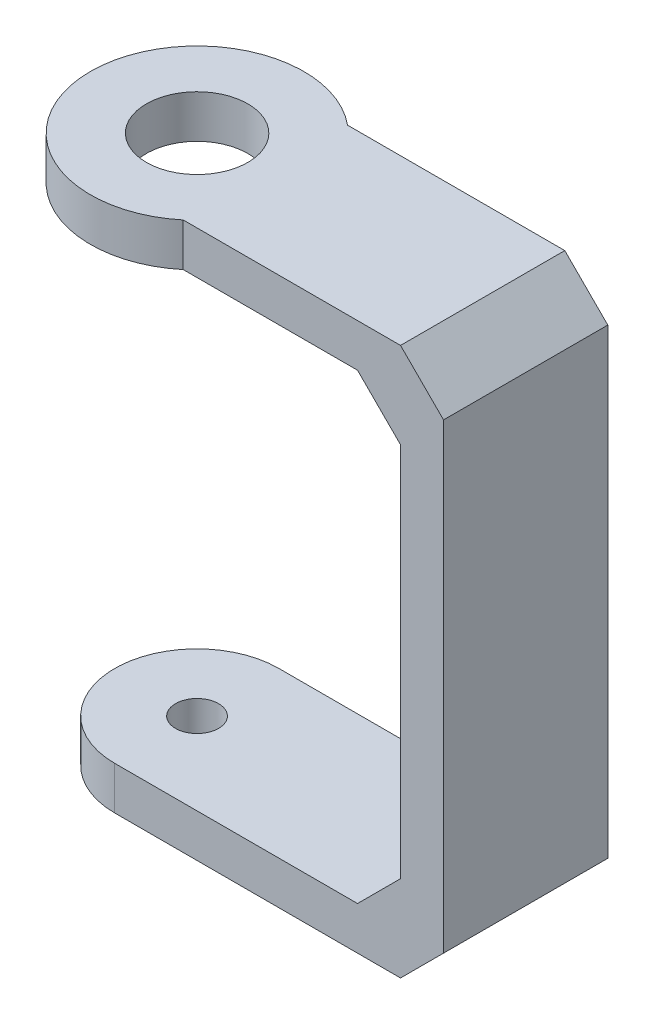
SolidWorks part; units mm, degrees
ref_plane "Front Plane" through (0, 0, 0) normal (0, 0, 1) x (1, 0, 0)
ref_plane "Top Plane" through (0, 0, 0) normal (0, 1, 0) x (1, 0, 0)
ref_plane "Right Plane" through (0, 0, 0) normal (1, 0, 0) x (0, 0, -1)
sketch "Sketch1" plane through (0, 0, 0) normal (0, 0, 1) x (1, 0, 0)
  line L0 (23.7361, 38.9968) -> (26.7361, 35.9968)
  line L1 (26.7361, 35.9968) -> (26.7361, 3.7768)
  line L2 (26.7361, 3.7768) -> (23.7361, 0.7768)
  line L3 (23.7361, 0.7768) -> (20.7361, 3.7768)
  line L4 (20.7361, 3.7768) -> (23.7361, 6.7768)
  line L7 (23.7361, 6.7768) -> (23.7361, 32.9968)
  line L8 (23.7361, 32.9968) -> (20.7361, 35.9968)
  line L9 (20.7361, 35.9968) -> (23.7361, 38.9968)
  point P2 (0, 0)
extrude "Boss-Extrude1" add sketch "Sketch1" along normal blind 5.73 and the other way blind 5.73
sketch "Sketch6" plane through (0, 0, 5.73) normal (0, 0, 1) x (1, 0, 0)
  line L0 (20.7361, 3.7768) -> (8.5761, 3.7768)
  line L1 (23.7361, 0.7768) -> (20.7361, 0.7768)
  line L3 (8.5761, 3.7768) -> (8.5761, 0.7768)
  line L4 (8.5761, 0.7768) -> (20.7361, 0.7768)
  line L5 (23.7361, 0.7768) -> (20.7361, 3.7768)
extrude "Boss-Extrude5" add sketch "Sketch6" against normal blind 11.46 contours L1 L4 L3 L0 L5
sketch "Sketch8" plane through (0, 0, 5.73) normal (0, 0, 1) x (1, 0, 0)
  line L1 (20.7361, 38.9968) -> (23.7361, 38.9968)
  line L2 (20.7361, 38.9968) -> (8.5761, 38.9968)
  line L3 (8.5761, 38.9968) -> (8.5761, 35.9968)
  line L4 (8.5761, 35.9968) -> (20.7361, 35.9968)
  line L5 (23.7361, 38.9968) -> (20.7361, 35.9968)
extrude "Boss-Extrude8" add sketch "Sketch8" against normal blind 11.46
sketch "Sketch9" plane through (0, 38.9968, 0) normal (0, 1, 0) x (1, 0, 0)
  line L0 (8.5761, 5.73) -> (8.5761, -5.73)
  arc A0 (8.5761, 5.73) -> (8.5761, -5.73) centre (3.8148, 0) ccw
extrude "Boss-Extrude9" add sketch "Sketch9" against normal blind 3
sketch "Sketch11" plane through (0, 38.9968, 0) normal (0, 1, 0) x (1, 0, 0)
  circle A1 centre (3.8148, 0) radius 3.54
extrude "Cut-Extrude1" cut sketch "Sketch11" against normal blind 3
sketch "Sketch12" plane through (0, 0.7768, 0) normal (0, -1, 0) x (-1, 0, 0)
  line L0 (-8.5761, 5.73) -> (-3.7931, 5.73)
  line L2 (-3.7931, -5.73) -> (-8.5761, -5.73)
  line L3 (-8.5761, -5.73) -> (-8.5761, 5.73)
  arc A0 (-3.7931, -5.73) -> (-3.7931, 5.73) centre (-3.7931, 0) ccw
extrude "Boss-Extrude10" add sketch "Sketch12" against normal blind 3
sketch "Sketch13" plane through (0, 3.7768, 0) normal (0, 1, 0) x (1, 0, 0)
  circle A0 centre (3.81, 0) radius 1.5
extrude "Cut-Extrude2" cut sketch "Sketch13" against normal blind 3
